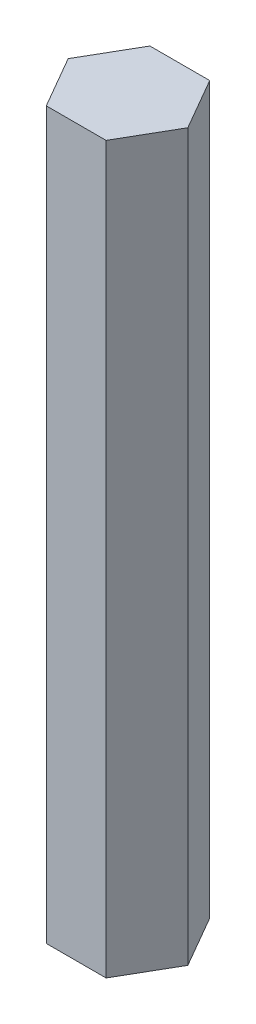
SolidWorks part; units mm, degrees
ref_plane "Front" through (0, 0, 0) normal (0, 0, 1) x (1, 0, 0)
ref_plane "Top" through (0, 0, 0) normal (0, 1, 0) x (1, 0, 0)
ref_plane "Right" through (0, 0, 0) normal (1, 0, 0) x (0, 0, -1)
sketch "Sketch1" plane through (0, 0, 0) normal (0, 1, 0) x (1, 0, 0)
  line L1 (7.3323, 0) -> (3.6662, 6.35)
  line L2 (3.6662, 6.35) -> (-3.6662, 6.35)
  line L3 (-3.6662, 6.35) -> (-7.3323, 0)
  line L4 (-7.3323, 0) -> (-3.6662, -6.35)
  line L5 (-3.6662, -6.35) -> (3.6662, -6.35)
  line L6 (3.6662, -6.35) -> (7.3323, 0)
  circle A0 centre (0, 0) radius 6.35 construction
  dimension "D1" = 12.7
extrude "Boss-Extrude1" add sketch "Sketch1" along normal mid plane 88.9
ref_axis "Axis1" through (0, 50, 0) along (0, -1, 0)
